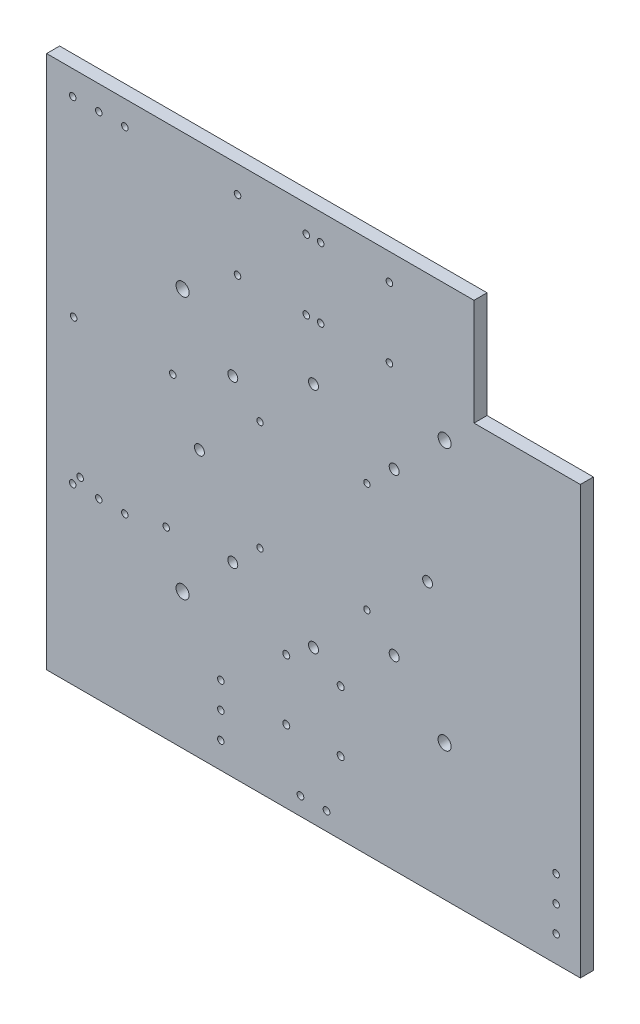
SolidWorks part; units mm, degrees
material "Perspex (TM) GS Acrylic Cast Sheet"
ref_plane "Front Plane" through (0, 0, 0) normal (0, 0, 1) x (1, 0, 0)
ref_plane "Top Plane" through (0, 0, 0) normal (0, 1, 0) x (1, 0, 0)
ref_plane "Right Plane" through (0, 0, 0) normal (1, 0, 0) x (0, 0, -1)
sketch "Sketch1" plane through (0, 0, 0) normal (0, 0, 1) x (1, 0, 0)
  line L0 (-130, 130) -> (130, 130)
  line L1 (130, 130) -> (130, -130)
  line L2 (130, -130) -> (-130, -130)
  line L3 (-130, -130) -> (-130, 130)
  line L4 (-120, 33.6598) -> (-120, -33.6505)
  line L5 (-29, 8) -> (-29, -8)
  line L6 (-29, 8) -> (-26.035, 8)
  line L7 (-26.035, 8) -> (-26.035, -8)
  line L8 (32.385, 33.02) -> (-32.385, 33.02)
  line L9 (-26.035, -8) -> (-29, -8)
  line L10 (-32.385, 33.02) -> (-32.385, -33.02)
  line L11 (-32.385, -33.02) -> (32.385, -33.02)
  line L12 (32.385, -33.02) -> (32.385, 33.02)
  line L13 (-107.2982, -46.3523) -> (-77.9253, -46.3523)
  line L14 (-113.65, 40.0098) -> (-71.5759, 40.0098)
  line L15 (-79.4148, 40.0098) -> (-79.4148, 22.9992)
  line L16 (-65.2259, -33.6529) -> (-65.2259, 33.6598)
  line L17 (-79.4148, 22.9992) -> (-94.8974, 22.9992)
  line L18 (-40, 120) -> (40, 120)
  line L19 (-94.8974, 22.9992) -> (-94.8974, 40.0098)
  line L31 (-40, 120) -> (-40, 80)
  line L32 (-40, 80) -> (40, 80)
  line L33 (40, 80) -> (40, 120)
  line L34 (-35, 100) -> (-35, 114.5)
  line L35 (-35, 114.5) -> (-29, 114.5)
  line L36 (-29, 114.5) -> (-29, 85.5)
  line L37 (-29, 85.5) -> (-35, 85.5)
  line L38 (-35, 85.5) -> (-35, 100)
  line L46 (16.75, -63) -> (16.75, -97)
  line L49 (16.75, -97) -> (-16.75, -97)
  line L50 (-16.75, -97) -> (-16.75, -63)
  line L51 (-16.75, -63) -> (16.75, -63)
  line L56 (120, 41.2) -> (120, -41.2)
  line L57 (45, 41.2) -> (45, -41.2)
  line L58 (120, 41.2) -> (45, 41.2)
  line L60 (45, -41.2) -> (120, -41.2)
  circle A0 centre (-26.035, 26.67) radius 1.55
  circle A1 centre (-26.035, -26.67) radius 1.55
  circle A2 centre (26.035, 26.67) radius 1.55
  circle A3 centre (26.035, -26.67) radius 1.55
  circle A4 centre (-116.825, 25.4027) radius 1.5875
  circle A5 centre (-113.65, -40.6352) radius 1.5875
  arc A6 (-120, -33.6505) -> (-107.2982, -46.3523) centre (-107.2982, -33.6505) ccw
  arc A7 (-77.9253, -46.3523) -> (-65.2259, -33.6529) centre (-77.9253, -33.6529) ccw
  arc A8 (-113.65, 40.0098) -> (-120, 33.6598) centre (-113.65, 33.6598) ccw
  arc A9 (-65.2259, 33.6598) -> (-71.5759, 40.0098) centre (-71.5759, 33.6598) ccw
  circle A10 centre (-68.565, 25.4048) radius 1.5875
  circle A11 centre (-37, 117) radius 1.6
  circle A12 centre (-37, 83) radius 1.6
  circle A13 centre (-3.5, 117) radius 1.6
  circle A14 centre (-3.5, 83) radius 1.6
  circle A15 centre (3.5, 117) radius 1.6
  circle A16 centre (37, 117) radius 1.6
  circle A17 centre (37, 83) radius 1.6
  circle A18 centre (3.5, 83) radius 1.6
  circle A19 centre (-13.25, -65.25) radius 1.7
  circle A20 centre (13.25, -65.25) radius 1.7
  circle A21 centre (13.25, -94.75) radius 1.7
  circle A22 centre (-13.25, -94.75) radius 1.7
  circle A23 centre (-76.33, 76.33) radius 3.175
  circle A24 centre (0, 55.575) radius 2.415
  circle A25 centre (-55.575, 0) radius 2.415
  circle A26 centre (0, -55.575) radius 2.415
  circle A27 centre (55.575, 0) radius 2.415
  circle A28 centre (-39.2975, 39.2975) radius 2.415
  circle A29 centre (39.2975, 39.2975) radius 2.415
  circle A30 centre (39.2975, -39.2975) radius 2.415
  circle A31 centre (-39.2975, -39.2975) radius 2.415
  circle A32 centre (76.33, 76.33) radius 3.175
  circle A33 centre (76.33, -76.33) radius 3.175
  circle A34 centre (-76.33, -76.33) radius 3.175
  arc A35 (-2.4144, 55.5225) -> (-37.5531, 40.9676) centre (0, 0) ccw
  arc A36 (37.5531, 40.9676) -> (2.4144, 55.5225) centre (0, 0) ccw
  arc A37 (55.5225, 2.4144) -> (40.9676, 37.5531) centre (0, 0) ccw
  arc A38 (40.9676, -37.5531) -> (55.5225, -2.4144) centre (0, 0) ccw
  arc A39 (2.4144, -55.5225) -> (37.5531, -40.9676) centre (0, 0) ccw
  arc A40 (-37.5531, -40.9676) -> (-2.4144, -55.5225) centre (0, 0) ccw
  arc A41 (-55.5225, -2.4144) -> (-40.9676, -37.5531) centre (0, 0) ccw
  arc A42 (-40.9676, 37.5531) -> (-55.5225, 2.4144) centre (0, 0) ccw
  circle A43 centre (-71.74, -40.6352) radius 1.5875
  circle A44 centre (6.35, -121.3) radius 1.651
  circle A45 centre (-6.35, -121.3) radius 1.651
  circle A46 centre (121.3, 126.35) radius 1.651
  circle A47 centre (121.3, 113.65) radius 1.651
  point P127 (127.65, 120)
  point P128 (-120, -120)
  point P129 (0, -127.65)
extrude "Boss-Extrude2" add sketch "Sketch1" along normal blind 6.35 contours L0 L1 L2 L3 | A10 | A43 | A5 | A4 | A25 | A28 | A24 | A31 | A26 | A30 | A27 | A29 | A1 | A3 | A2 | A0 | A22 | A21 | A20 | A19 | A45 | A44 | A46 | A47 | A17 | A16 | A18 | A14 | A15 | A13 | A11 | A12
sketch "Sketch2" plane through (0, 0, 0) normal (0, 0, -1) x (-1, 0, 0)
  circle A0 centre (0, 0) radius 55.6086 construction
sketch "Sketch5" plane through (0, 0, 0) normal (0, 0, -1) x (-1, 0, 0)
  line L0 (-78.2, 78.2) -> (-78.2, 131)
  line L1 (-78.2, 131) -> (-131, 131)
  line L2 (-131, 131) -> (-131, 78.2)
  line L3 (-131, 78.2) -> (-78.2, 78.2)
  line L4 (-130, 130) -> (-130, 79.2)
  line L5 (-130, 79.2) -> (-79.2, 79.2)
  line L6 (-79.2, 79.2) -> (-79.2, 130)
  line L7 (-79.2, 130) -> (-130, 130)
  line L8 (-130, 130) -> (-130, 79.2)
  line L9 (-130, 79.2) -> (-79.2, 79.2)
  line L10 (-79.2, 79.2) -> (-79.2, 130)
  line L11 (-79.2, 130) -> (-130, 130)
  dimension "D1" = 0
  dimension "D2" = 1
extrude "Cut-Extrude1" cut sketch "Sketch5" against normal through all contours L2 L3 L0 L1
sketch "Sketch6" plane through (0, 0, 0) normal (0, 0, -1) x (-1, 0, 0)
  circle A0 centre (63.7786, 63.7786) radius 3.175 construction
  circle A1 centre (-63.8746, 63.7786) radius 3.175 construction
  circle A2 centre (-63.8746, -63.8746) radius 3.175 construction
  circle A3 centre (63.7786, -63.8746) radius 3.175 construction
  circle A4 centre (63.7786, 63.7786) radius 3.175
  circle A5 centre (-63.8746, 63.7786) radius 3.175
  circle A6 centre (-63.8746, -63.8746) radius 3.175
  circle A7 centre (63.7786, -63.8746) radius 3.175
extrude "Cut-Extrude2" cut sketch "Sketch6" against normal through all contours A7 | A6 | A5 | A4
sketch "Sketch7" plane through (0, 0, 0) normal (0, 0, -1) x (-1, 0, 0)
  circle A0 centre (91.9, 118.189) radius 1.5875 construction
  circle A1 centre (104.6, 118.189) radius 1.5875 construction
  circle A2 centre (117.3, 118.189) radius 1.5875 construction
  circle A3 centre (91.9, -45.133) radius 1.5875 construction
  circle A4 centre (104.6, -45.133) radius 1.5875 construction
  circle A5 centre (117.3, -45.133) radius 1.5875 construction
  circle A6 centre (45.133, -117.3) radius 1.5875 construction
  circle A7 centre (45.133, -104.6) radius 1.5875 construction
  circle A8 centre (45.133, -91.9) radius 1.5875 construction
  circle A9 centre (-118.189, -117.3) radius 1.5875 construction
  circle A10 centre (-118.189, -104.6) radius 1.5875 construction
  circle A11 centre (-118.189, -91.9) radius 1.5875 construction
  circle A12 centre (91.9, 118.189) radius 1.5875
  circle A13 centre (104.6, 118.189) radius 1.5875
  circle A14 centre (117.3, 118.189) radius 1.5875
  circle A15 centre (91.9, -45.133) radius 1.5875
  circle A16 centre (104.6, -45.133) radius 1.5875
  circle A17 centre (117.3, -45.133) radius 1.5875
  circle A18 centre (45.133, -117.3) radius 1.5875
  circle A19 centre (45.133, -104.6) radius 1.5875
  circle A20 centre (45.133, -91.9) radius 1.5875
  circle A21 centre (-118.189, -117.3) radius 1.5875
  circle A22 centre (-118.189, -104.6) radius 1.5875
  circle A23 centre (-118.189, -91.9) radius 1.5875
extrude "Cut-Extrude3" cut sketch "Sketch7" against normal through all
